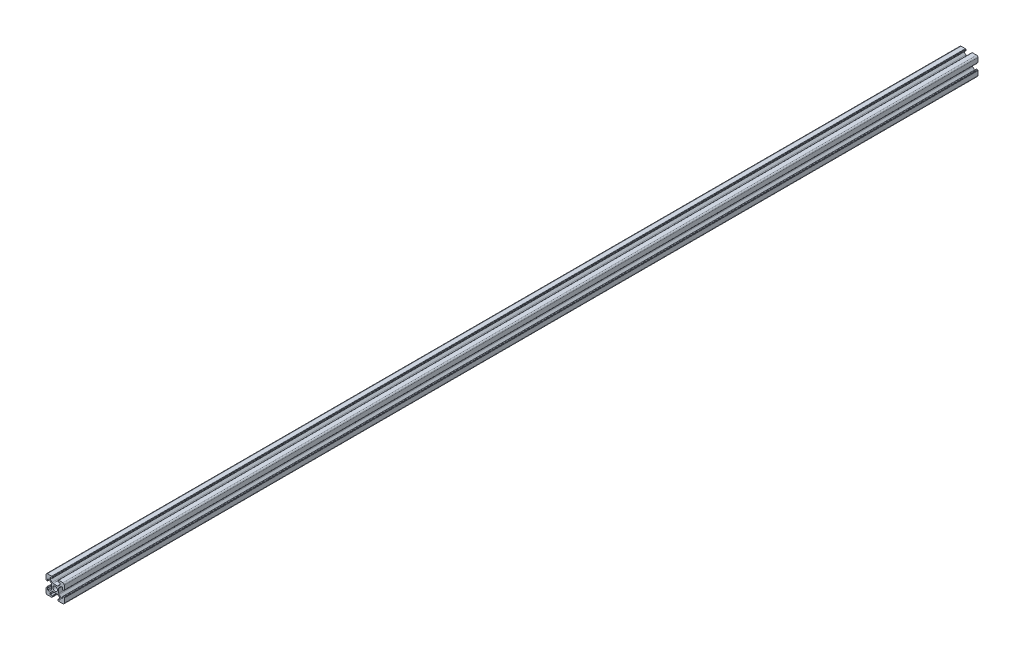
SolidWorks part; units mm, degrees
material "1060 Alloy"
ref_plane "Front Plane" through (0, 0, 0) normal (0, 0, 1) x (1, 0, 0)
ref_plane "Top Plane" through (0, 0, 0) normal (0, 1, 0) x (1, 0, 0)
ref_plane "Right Plane" through (0, 0, 0) normal (1, 0, 0) x (0, 0, -1)
sketch "Sketch1" plane through (0, 0, 0) normal (0, 0, 1) x (1, 0, 0)
  line L0 (3.8995, 3.9005) -> (10.4604, 10.4604) construction
  line L2 (-3.9002, 2.2177) -> (-3.9002, -2.2208)
  line L5 (-3.9005, 3.899) -> (3.9001, -3.8986) construction
  line L6 (-3.9, -3.901) -> (3.8995, 3.9005) construction
  line L7 (-0.0002, 10) -> (-0.0002, -9.9996) construction
  line L8 (-0.0002, -9.9996) -> (-0.0002, 10) construction
  line L9 (5.5006, 6.5619) -> (3.2793, 4.3405)
  line L14 (-10.0002, 9.9996) -> (9.9994, -10) construction
  line L15 (-9.9999, -10.0001) -> (9.9998, 10) construction
  line L16 (6.5613, 5.5012) -> (4.3401, 3.28)
  line L17 (-5.5002, 6.5603) -> (-3.279, 4.3391)
  line L18 (-6.5609, 5.4996) -> (-4.3395, 3.2783)
  line L19 (7.9206, 5.5012) -> (6.5613, 5.5012)
  line L20 (8.2006, 3.3812) -> (8.2006, 5.2212)
  line L21 (9.4206, 3.1012) -> (8.4806, 3.1012)
  line L22 (9.7006, 3.6012) -> (9.7006, 3.3812)
  line L23 (-8.5002, 9.9996) -> (-3.8802, 9.9996)
  line L24 (-3.6002, 9.7196) -> (-3.6002, 9.6996)
  line L25 (-3.6002, 9.6996) -> (-3.3802, 9.6996)
  line L26 (-3.1002, 9.4196) -> (-3.1002, 8.4796)
  line L27 (-3.3802, 8.1996) -> (-5.2202, 8.1996)
  line L28 (-5.5002, 7.9196) -> (-5.5002, 6.5603)
  line L29 (-7.9202, 5.4996) -> (-6.5609, 5.4996)
  line L30 (-8.2002, 3.3796) -> (-8.2002, 5.2196)
  line L31 (-9.4202, 3.0996) -> (-8.4802, 3.0996)
  line L32 (-9.7202, 3.5996) -> (-9.7002, 3.5996)
  line L33 (-9.7002, 3.5996) -> (-9.7002, 3.3796)
  line L34 (-10.0002, 8.4996) -> (-10.0002, 3.8796)
  line L35 (10.0006, 8.5012) -> (10.0006, 3.8812)
  line L36 (8.5006, 10.0012) -> (3.8806, 10.0012)
  line L37 (3.6006, 9.7012) -> (3.3806, 9.7012)
  line L38 (3.1006, 9.4212) -> (3.1006, 8.4812)
  line L39 (3.3806, 8.2012) -> (5.2206, 8.2012)
  line L40 (5.5006, 7.9212) -> (5.5006, 6.5619)
  line L41 (6.5629, -5.4996) -> (4.3415, -3.2783)
  line L42 (5.5022, -6.5603) -> (3.281, -4.3391)
  line L43 (5.5022, -7.9196) -> (5.5022, -6.5603)
  line L44 (3.3822, -8.1996) -> (5.2222, -8.1996)
  line L45 (3.1022, -9.4196) -> (3.1022, -8.4796)
  line L46 (3.6022, -9.6996) -> (3.3822, -9.6996)
  line L47 (8.5022, -9.9996) -> (3.8822, -9.9996)
  line L48 (10.0022, -8.4996) -> (10.0022, -3.8796)
  line L49 (9.7022, -3.5996) -> (9.7022, -3.3796)
  line L50 (9.4222, -3.0996) -> (8.4822, -3.0996)
  line L51 (8.2022, -3.3796) -> (8.2022, -5.2196)
  line L52 (7.9222, -5.4996) -> (6.5629, -5.4996)
  line L53 (-5.4986, -6.5619) -> (-3.2773, -4.3405)
  line L54 (-6.5593, -5.5012) -> (-4.3395, -3.2814)
  line L55 (-7.9186, -5.5012) -> (-6.5593, -5.5012)
  line L56 (-8.1986, -3.3812) -> (-8.1986, -5.2212)
  line L57 (-9.4186, -3.1012) -> (-8.4786, -3.1012)
  line L58 (-9.6986, -3.6012) -> (-9.6986, -3.3812)
  line L59 (-9.9986, -8.5012) -> (-9.9986, -3.8812)
  line L60 (-8.4986, -10.0012) -> (-3.8786, -10.0012)
  line L61 (-3.5986, -9.7012) -> (-3.3786, -9.7012)
  line L62 (-3.0986, -9.4212) -> (-3.0986, -8.4812)
  line L63 (-3.3786, -8.2012) -> (-5.2186, -8.2012)
  line L64 (-5.4986, -7.9212) -> (-5.4986, -6.5619)
  line L65 (-2.233, 3.8998) -> (2.2187, 3.9012)
  line L66 (3.9008, 2.234) -> (3.9022, -2.2177)
  line L67 (2.235, -3.8998) -> (-2.2167, -3.9012)
  line L68 (3.6006, 9.7212) -> (3.6006, 9.6996)
  line L69 (9.7006, 3.6012) -> (9.7206, 3.6012)
  line L70 (-9.6986, -3.6012) -> (-9.7186, -3.6012)
  line L71 (-3.5986, -9.7012) -> (-3.5986, -9.7212)
  line L72 (3.6022, -9.6996) -> (3.6022, -9.7196)
  line L73 (9.7222, -3.5996) -> (9.7022, -3.5996)
  arc A0 (-3.6002, 9.7196) -> (-3.8802, 9.9996) centre (-3.8802, 9.7196) ccw
  arc A1 (-3.3802, 9.6996) -> (-3.1002, 9.4196) centre (-3.3802, 9.4196) cw
  arc A2 (-3.1002, 8.4796) -> (-3.3802, 8.1996) centre (-3.3802, 8.4796) cw
  arc A3 (-10.0002, 8.4996) -> (-8.5002, 9.9996) centre (-8.5002, 8.4996) cw
  arc A4 (-8.2002, 3.3796) -> (-8.4802, 3.0996) centre (-8.4802, 3.3796) cw
  arc A5 (-9.4202, 3.0996) -> (-9.7002, 3.3796) centre (-9.4202, 3.3796) cw
  arc A6 (-9.7202, 3.5996) -> (-10.0002, 3.8796) centre (-9.7202, 3.8796) cw
  arc A7 (-3.279, 4.3391) -> (-2.233, 3.8998) centre (-2.2183, 5.3997) ccw
  arc A8 (-4.3395, 3.2783) -> (-3.9002, 2.2177) centre (-5.4002, 2.2177) cw
  arc A9 (-7.9202, 5.4996) -> (-8.2002, 5.2196) centre (-7.9202, 5.2196) ccw
  arc A10 (-5.2202, 8.1996) -> (-5.5002, 7.9196) centre (-5.2202, 7.9196) ccw
  arc A12 (-4.3395, -3.2814) -> (-3.9002, -2.2208) centre (-5.4002, -2.2208) ccw
  arc A13 (8.2006, 5.2212) -> (7.9206, 5.5012) centre (7.9206, 5.2212) ccw
  arc A14 (8.4806, 3.1012) -> (8.2006, 3.3812) centre (8.4806, 3.3812) cw
  arc A15 (9.7006, 3.3812) -> (9.4206, 3.1012) centre (9.4206, 3.3812) cw
  arc A16 (9.7206, 3.6012) -> (10.0006, 3.8812) centre (9.7206, 3.8812) ccw
  arc A17 (8.5006, 10.0012) -> (10.0006, 8.5012) centre (8.5006, 8.5012) cw
  arc A18 (3.6006, 9.7212) -> (3.8806, 10.0012) centre (3.8806, 9.7212) cw
  arc A19 (3.1006, 9.4212) -> (3.3806, 9.7012) centre (3.3806, 9.4212) cw
  arc A20 (3.3806, 8.2012) -> (3.1006, 8.4812) centre (3.3806, 8.4812) cw
  arc A21 (5.5006, 7.9212) -> (5.2206, 8.2012) centre (5.2206, 7.9212) ccw
  arc A22 (3.2793, 4.3405) -> (2.2187, 3.9012) centre (2.2187, 5.4012) cw
  arc A23 (4.3401, 3.28) -> (3.9008, 2.234) centre (5.4007, 2.2193) ccw
  arc A25 (5.2222, -8.1996) -> (5.5022, -7.9196) centre (5.2222, -7.9196) ccw
  arc A26 (3.1022, -8.4796) -> (3.3822, -8.1996) centre (3.3822, -8.4796) cw
  arc A27 (3.3822, -9.6996) -> (3.1022, -9.4196) centre (3.3822, -9.4196) cw
  arc A28 (3.6022, -9.7196) -> (3.8822, -9.9996) centre (3.8822, -9.7196) ccw
  arc A29 (10.0022, -8.4996) -> (8.5022, -9.9996) centre (8.5022, -8.4996) cw
  arc A30 (9.7222, -3.5996) -> (10.0022, -3.8796) centre (9.7222, -3.8796) cw
  arc A31 (9.4222, -3.0996) -> (9.7022, -3.3796) centre (9.4222, -3.3796) cw
  arc A32 (8.2022, -3.3796) -> (8.4822, -3.0996) centre (8.4822, -3.3796) cw
  arc A33 (7.9222, -5.4996) -> (8.2022, -5.2196) centre (7.9222, -5.2196) ccw
  arc A34 (4.3415, -3.2783) -> (3.9022, -2.2177) centre (5.4022, -2.2177) cw
  arc A35 (3.281, -4.3391) -> (2.235, -3.8998) centre (2.2203, -5.3997) ccw
  circle A36 centre (0.001, -0.001) radius 2.5 construction
  arc A37 (-8.1986, -5.2212) -> (-7.9186, -5.5012) centre (-7.9186, -5.2212) ccw
  arc A38 (-8.4786, -3.1012) -> (-8.1986, -3.3812) centre (-8.4786, -3.3812) cw
  arc A39 (-9.6986, -3.3812) -> (-9.4186, -3.1012) centre (-9.4186, -3.3812) cw
  arc A40 (-9.7186, -3.6012) -> (-9.9986, -3.8812) centre (-9.7186, -3.8812) ccw
  arc A41 (-8.4986, -10.0012) -> (-9.9986, -8.5012) centre (-8.4986, -8.5012) cw
  arc A42 (-3.5986, -9.7212) -> (-3.8786, -10.0012) centre (-3.8786, -9.7212) cw
  arc A43 (-3.0986, -9.4212) -> (-3.3786, -9.7012) centre (-3.3786, -9.4212) cw
  arc A44 (-3.3786, -8.2012) -> (-3.0986, -8.4812) centre (-3.3786, -8.4812) cw
  arc A45 (-5.4986, -7.9212) -> (-5.2186, -8.2012) centre (-5.2186, -7.9212) ccw
  arc A46 (-3.2773, -4.3405) -> (-2.2167, -3.9012) centre (-2.2167, -5.4012) cw
  arc A48 (-4.3381, -3.28) -> (-3.8988, -2.234) centre (-5.3987, -2.2193) ccw [skipped]
  point P0 (0, 0)
  point P9 (-0.0002, 0.0002)
  point P12 (-0.0003, -0.0003)
  point P43 (-3.6002, 9.9996)
  point P46 (-3.1002, 9.6996)
  point P49 (-3.1002, 8.1996)
  point P55 (-8.2002, 3.0996)
  point P58 (-9.7002, 3.0996)
  point P61 (-10.0002, 3.5996)
  point P64 (-2.8395, 3.8996)
  point P67 (-3.9002, 2.839)
  point P70 (-8.2002, 5.4996)
  point P73 (-5.5002, 8.1996)
  point P184 (0.001, 0)
  dimension "D14" = 0.28
  dimension "D15" = 0.28
  dimension "D16" = 0.28
  dimension "D17" = 1.5
  dimension "D18" = 0.28
  dimension "D19" = 1.5
  dimension "D20" = 1.5
  dimension "D21" = 0.28
  dimension "D23" = 5
  dimension "D27" = 1.5
  dimension "D1" = 7.8
  dimension "D2" = 7.8
  dimension "D3" = 3.1
  dimension "D4" = 3.6
  dimension "D5" = 20
  dimension "D6" = 20
  dimension "D7" = 0.75
  dimension "D8" = 1.8
  dimension "D9" = 5.5
  dimension "D10" = 6.4
  dimension "D11" = 6.4
  dimension "D12" = 3.7627
  dimension "D13" = 0.3
  dimension "D24" = 4.62
  dimension "D25" = 3.9005
  dimension "D26" = 7.801
  dimension "D22" = 4
extrude "Boss-Extrude1" add sketch "Sketch1" along normal blind 1000 contours L53 A46 L67 A35 L42 L43 A25 L44 A26 L45 A27 L46 L72 A28 L47 A29 L48 A30 L73 L49 A31 L50 A32 L51 A33 L52 L41 A34 L66 A23 L16 L19 A13 L20 A14 L21 A15 L22 L69 A16 L35 A17 L36 A18 L68 L37 A19 L38 A20 region at (0.0009, 0, 0)
sketch3d "3DSketch2"
  circle A0 centre (0, 0, 0) radius 2.5
  point P2 (0, 0, 2.5)
extrude "Cut-Extrude1" cut sketch "3DSketch2" along direction (0, 0, 1) on the side of the normal through all contours A0
